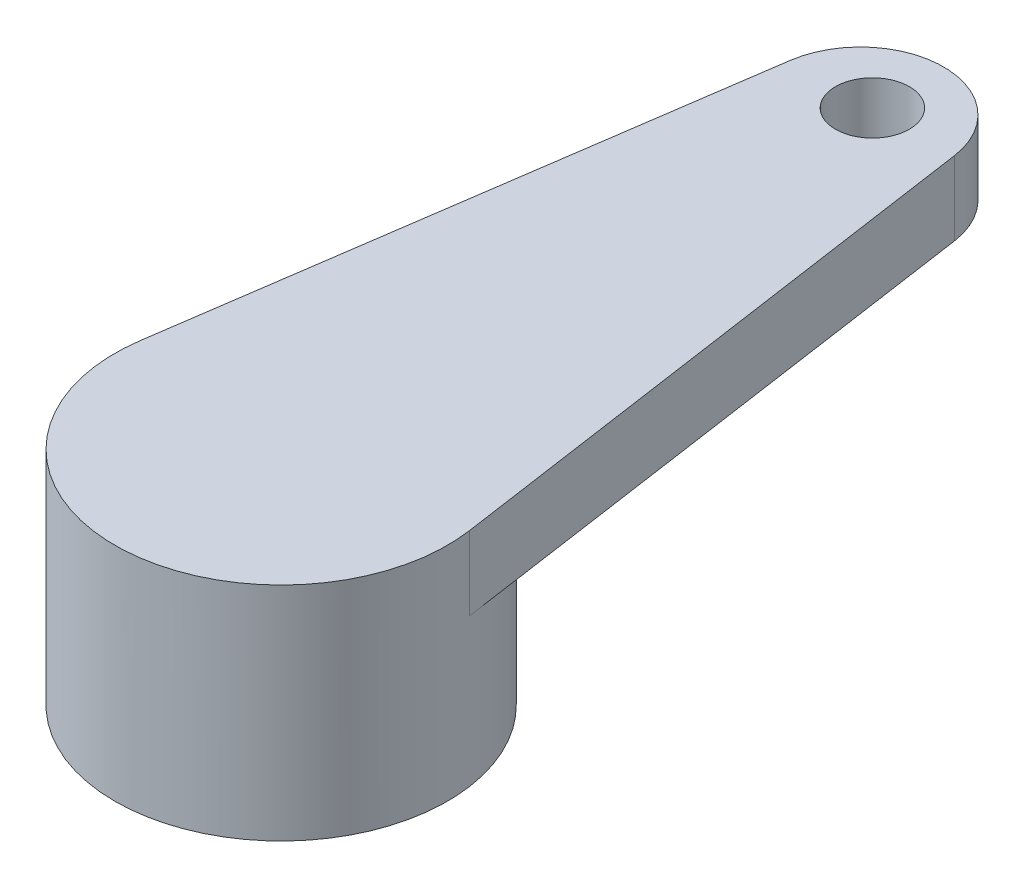
SolidWorks part; units mm, degrees
material "ABS"
ref_plane "Front Plane" through (0, 0, 0) normal (0, 0, 1) x (1, 0, 0)
ref_plane "Top Plane" through (0, 0, 0) normal (0, 1, 0) x (1, 0, 0)
ref_plane "Right Plane" through (0, 0, 0) normal (1, 0, 0) x (0, 0, -1)
sketch "Sketch1" plane through (0, 0, 0) normal (0, 1, 0) x (1, 0, 0)
  circle A0 centre (0, 0) radius 3
  circle A1 centre (0, 0) radius 4.5
  dimension "D1" = 6
  dimension "D2" = 9
extrude "Boss-Extrude1" add sketch "Sketch1" along normal blind 4
sketch "Sketch2" plane through (0, 4, 0) normal (0, 1, 0) x (1, 0, 0)
  line L0 (0, 0) -> (0, 16) construction
  line L1 (-4.4534, 0.6458) -> (-2.2267, 16)
  line L2 (4.4534, 0.6458) -> (2.2267, 16)
  line L3 (-2.2267, 16) -> (2.2267, 16) construction
  circle A0 centre (0, 0) radius 4.5 construction
  arc A1 (-2.2267, 16) -> (2.2267, 16) centre (0, 15.6771) cw
  circle A2 centre (0, 16) radius 1
  arc A3 (-4.4534, 0.6458) -> (4.4534, 0.6458) centre (0, 0) ccw
  dimension "D2" = 2
  dimension "D3" = 2.25
  dimension "D1" = 16
extrude "Boss-Extrude2" add sketch "Sketch2" along normal blind 2
ref_axis "Axis1" through (0, -0.3, 0) along (0, 1, 0)
